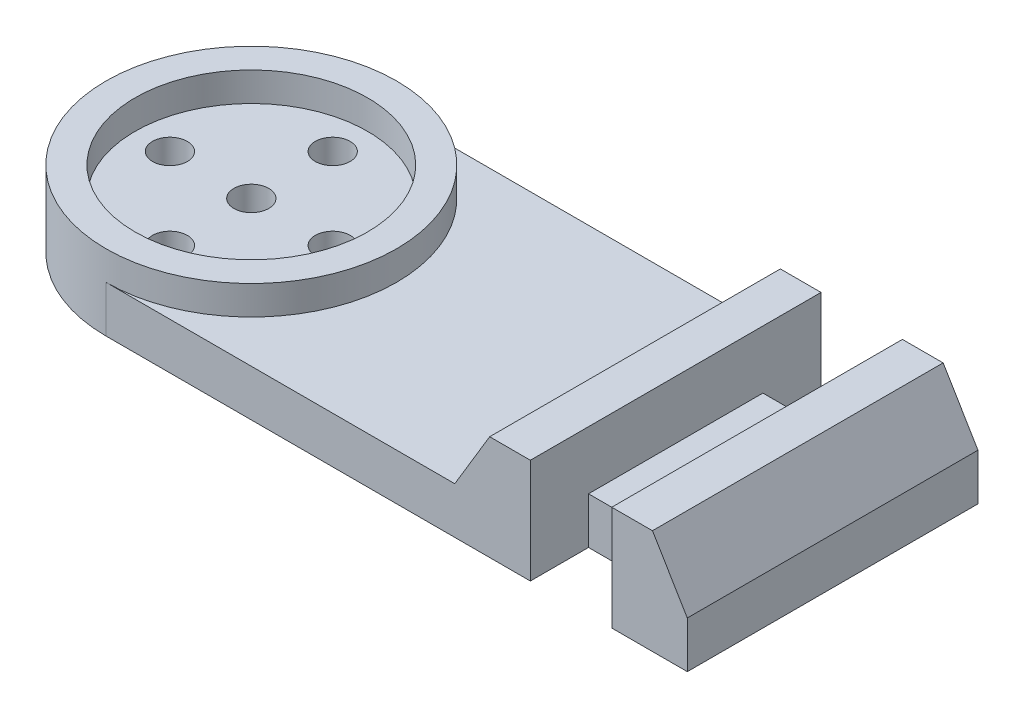
SolidWorks part; units mm, degrees
material "ABS"
ref_plane "前视基准面" through (0, 0, 0) normal (0, 0, 1) x (1, 0, 0)
ref_plane "上视基准面" through (0, 0, 0) normal (0, 1, 0) x (1, 0, 0)
ref_plane "右视基准面" through (0, 0, 0) normal (1, 0, 0) x (0, 0, -1)
sketch "草图1" plane through (0, 0, 0) normal (0, 1, 0) x (1, 0, 0)
  line L0 (0, 12.5) -> (50, 12.5)
  line L1 (0, -12.5) -> (50, -12.5)
  line L2 (50, 12.5) -> (50, -12.5)
  circle A0 centre (0, 0) radius 12.5
  dimension "D1" = 25
  dimension "D2" = 50
extrude "凸台-拉伸1" add sketch "草图1" along normal blind 4 contours A0 | A0 L1 L2 L0 region at (29.8119, 0, 0) region at (0, 0, 0)
sketch "草图2" plane through (0, 4, 0) normal (0, 1, 0) x (1, 0, 0)
  circle A0 centre (0, 0) radius 12.5
  circle A1 centre (0, 0) radius 10
  dimension "D1" = 25
  dimension "D2" = 20
extrude "凸台-拉伸2" add sketch "草图2" along normal blind 2.5
sketch "草图3" plane through (0, 0, 0) normal (0, -1, 0) x (1, 0, 0)
  line L0 (0, 16.9978) -> (0, -21.3221) construction
  line L1 (-30.6103, 0) -> (69.188, 0) construction
  circle A0 centre (0, 0) radius 1.5
  circle A1 centre (0, 7) radius 1.5
  circle A2 centre (7, 0) radius 1.5
  circle A3 centre (0, -7) radius 1.5
  circle A4 centre (-7, 0) radius 1.5
  circle A5 centre (40, 0) radius 1.5
  dimension "D1" = 3
  dimension "D2" = 3
  dimension "D5" = 3
  dimension "D3" = 7
  dimension "D6" = 40
  dimension "D4" = 4
extrude "切除-拉伸1" cut sketch "草图3" against normal through all
sketch "草图4" plane through (0, 0, 12.5) normal (0, 0, 1) x (1, 0, 0)
  line L0 (40, 14.1176) -> (40, -14.2645) construction
  line L2 (50, 4) -> (47, 9)
  line L3 (47, 9) -> (33, 9)
  line L4 (0, 4) -> (50, 4) construction
  line L5 (30, 4) -> (33, 9)
  line L6 (30, 4) -> (50, 4)
  point P11 (40, 9)
  dimension "D1" = 40
  dimension "D2" = 7
  dimension "D3" = 5
extrude "凸台-拉伸3" add sketch "草图4" against normal up to surface (25 mm away) up to face at (25, 2, -12.5)
sketch "草图5" plane through (0, 0, 12.5) normal (0, 0, 1) x (1, 0, 0)
  line L0 (40, 19.3346) -> (40, -11.3346) construction
  line L1 (36.5, 9) -> (43.5, 9)
  line L2 (47, 9) -> (33, 9) construction
  line L3 (43.5, 9) -> (43.5, 4)
  line L4 (43.5, 4) -> (36.5, 4)
  line L5 (36.5, 9) -> (36.5, 4)
  point P10 (40, 4)
  point P11 (40, 9)
  dimension "D1" = 40
  dimension "D2" = 3.5
  dimension "D3" = 5
extrude "切除-拉伸2" cut sketch "草图5" against normal through all
sketch "草图6" plane through (0, 4, 0) normal (0, 1, 0) x (1, 0, 0)
  line L0 (36.5, -12.5) -> (43.5, -12.5)
  line L1 (43.5, -12.5) -> (43.5, -7.5)
  line L2 (43.5, -7.5) -> (36.5, -7.5)
  line L3 (36.5, 12.5) -> (36.5, -12.5) construction
  line L4 (36.5, -7.5) -> (36.5, -12.5)
  line L5 (-16.7425, 0) -> (62.5585, 0) construction
  line L6 (36.5, 12.5) -> (43.5, 12.5)
  line L7 (36.5, 7.5) -> (36.5, 12.5)
  line L8 (43.5, 12.5) -> (43.5, 7.5)
  line L9 (43.5, 7.5) -> (36.5, 7.5)
  dimension "D1" = 5
extrude "切除-拉伸3" cut sketch "草图6" against normal through all
